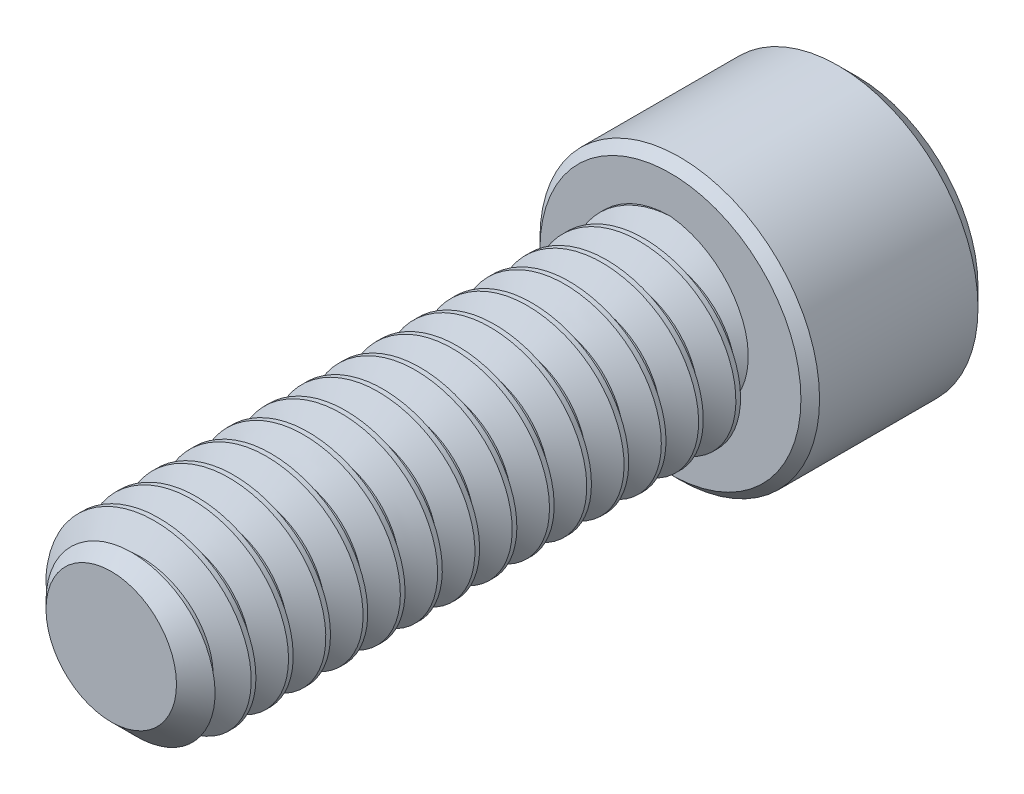
SolidWorks part; units mm, degrees
ref_plane "Front Plane" through (0, 0, 0) normal (0, 0, 1) x (1, 0, 0)
ref_plane "Top Plane" through (0, 0, 0) normal (0, 1, 0) x (1, 0, 0)
ref_plane "Right Plane" through (0, 0, 0) normal (1, 0, 0) x (0, 0, -1)
sketch "Sketch1" plane through (0, 0, 0) normal (0, 0, 1) x (1, 0, 0)
  line L0 (0, 3.175) -> (0, -3.175) construction
  circle A0 centre (0, 0) radius 3.175
  dimension "OD" = 6.35
extrude "Extrude1" add sketch "Sketch1" against normal blind 19.05
sketch "Sketch2" plane through (0, 0, 0) normal (0, 0, 1) x (1, 0, 0)
  circle A0 centre (0, 0) radius 3.175 construction
  circle A1 centre (0, 0) radius 3.175
curve "Helix/Spiral1" pitch 1.27 height 20.32 turns 16 parameters "pitch"=1.27
chamfer "Chamfer3" distance 0.9525 angle 45 1 edges at (3.175, 0, 0)
sketch "Sketch3" plane through (0, 0, 0) normal (1, 0, 0) x (0, 0, -1)
  line L0 (-1.1113, 3.175) -> (-0.635, 2.3501)
  line L1 (-0.635, 2.3501) -> (-0.4763, 2.3501)
  line L2 (-0.4763, 2.3501) -> (0, 3.175)
  line L3 (-1.1113, 3.175) -> (0, 3.175)
  line L4 (-0.5556, 3.175) -> (-0.5556, 2.3501) construction
  line L5 (-0.8731, 2.7626) -> (-0.2381, 2.7626) construction
  line L6 (0, 3.175) -> (0, -3.175) construction
  dimension "D1" = 0.1588
  dimension "D2" = 0.635
  dimension "D3" = 60
sweep "Cut-Sweep1" cut profiles "Sketch3" path "Helix/Spiral1"
sketch "Sketch6" plane through (0, 0, -19.05) normal (0, 0, -1) x (-1, 0, 0)
  circle A0 centre (0, 0) radius 4.7625
  dimension "head dia" = 9.525
extrude "Extrude2" add sketch "Sketch6" along normal blind 6.35
sketch "Sketch7" plane through (0, 0, -25.4) normal (0, 0, -1) x (-1, 0, 0)
  line L1 (0, 2.7496) -> (-2.3812, 1.3748)
  line L2 (-2.3812, 1.3748) -> (-2.3812, -1.3748)
  line L3 (-2.3812, -1.3748) -> (0, -2.7496)
  line L4 (0, -2.7496) -> (2.3812, -1.3748)
  line L5 (2.3812, -1.3748) -> (2.3812, 1.3748)
  line L6 (2.3812, 1.3748) -> (0, 2.7496)
  circle A0 centre (0, 0) radius 2.3813 construction
  dimension "hex dia" = 4.7625
extrude "Cut-Extrude1" cut sketch "Sketch7" against normal blind 3.5719
sketch "Sketch8" plane through (0, 0, -25.4) normal (0, 0, -1) x (-1, 0, 0)
  circle A0 centre (0, 0) radius 2.7496
extrude "Cut-Extrude2" cut sketch "Sketch8" against normal blind 0.635 draft 45
chamfer "Chamfer1" distance 0.635 angle 45 1 edges at (-4.7625, 0, -25.4)
chamfer "Chamfer2" distance 0.3175 angle 45 1 edges at (-4.7625, 0, -19.05)
sketch "Sketch9" plane through (0, 0, 0) normal (1, 0, 0) x (0, 0, -1)
  line L0 (0, 3.175) -> (0, -3.175) construction
  line L1 (6.985, 3.175) -> (6.985, -3.175) construction
  line L2 (19.05, 4.7625) -> (19.05, -4.7625) construction
  line L3 (25.4, 4.7625) -> (25.4, -4.7625) construction
  line L4 (25.4, 0) -> (0, 0) construction
  dimension "D1" = 6.985
  dimension "D2" = 6.35
  dimension "D3" = 9.525
  dimension "D4" = 19.05
equation "\"D3@Helix/Spiral1\" = \"screw length@Extrude1\"+\"pitch@Helix/Spiral1\""
equation "\"D1@Sketch3\" = \"pitch@Helix/Spiral1\"*.125"
equation "\"D2@Sketch3\" = \"pitch@Helix/Spiral1\"*.5"
equation "\"D1@Cut-Extrude1\" = \"hex dia@Sketch7\"*.75"
equation "\"D1@Chamfer1\" = \"head depth@Extrude2\"/10"
equation "\"D1@Sketch9\" = \"pitch@Helix/Spiral1\"*5.5"
equation "\"D1@Chamfer2\" = \"D1@Chamfer1\"/2"
equation "\"D1@Cut-Extrude2\" = \"D1@Chamfer2\"*2"
equation "\"D1@Chamfer3\" = \"pitch@Helix/Spiral1\"*.750"
equation "\"D2@Sketch9\" = \"head depth@Extrude2\""
equation "\"D3@Sketch9\" = \"head dia@Sketch6\""
equation "\"D4@Sketch9\" = \"screw length@Extrude1\""
